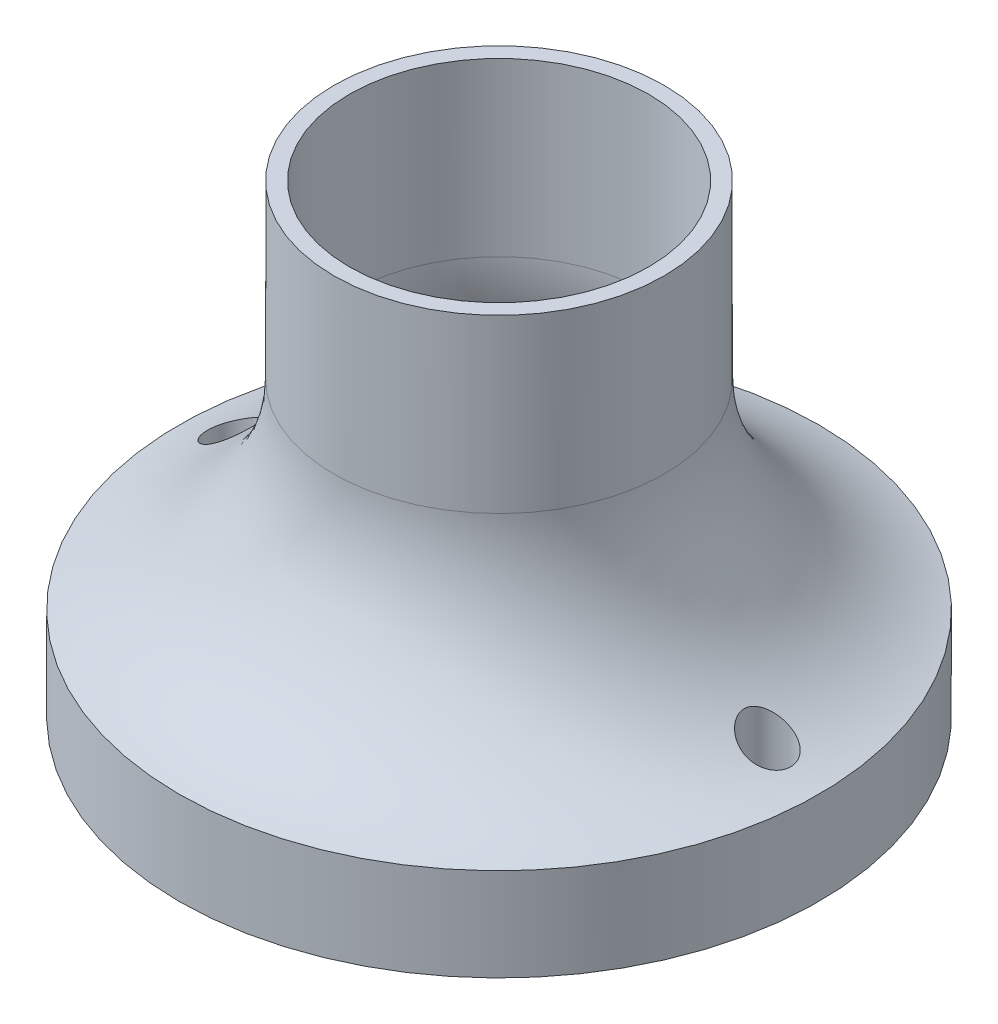
SolidWorks part; units mm, degrees
ref_plane "Front Plane" through (0, 0, 0) normal (0, 0, 1) x (1, 0, 0)
ref_plane "Top Plane" through (0, 0, 0) normal (0, 1, 0) x (1, 0, 0)
ref_plane "Right Plane" through (0, 0, 0) normal (1, 0, 0) x (0, 0, -1)
sketch "Sketch1" plane through (0, 0, 0) normal (0, 1, 0) x (1, 0, 0)
  circle A0 centre (0, 0) radius 31
  dimension "D1" = 62
extrude "Boss-Extrude1" add sketch "Sketch1" along normal blind 9
sketch "Sketch2" plane through (0, 9, 0) normal (0, 1, 0) x (1, 0, 0)
  circle A0 centre (0, 0) radius 16
  dimension "D1" = 32
extrude "Boss-Extrude2" add sketch "Sketch2" along normal blind 36
fillet "Fillet1" radius 20 1 edges at (0, 9, 16)
hole_wizard "Ø4.5 (4.5) Diameter Hole1" positions "Sketch5" profile "Sketch4" hole size "Ø4.5" standard "ISO" end condition through all
sketch "Sketch5" plane through (0, 0, 0) normal (0, -1, 0) x (-1, 0, 0)
  line L0 (26, 0) -> (-26, 0) construction
  point P1 (26, 0)
  point P2 (-26, 0)
  dimension "D1" = 52
sketch "Sketch4" plane through (-26, 0, 0) normal (1, 0, 0) x (0, 0, -1)
  line L0 (0, 0) -> (0, 45)
  line L1 (0, 45) -> (2.25, 45)
  line L2 (2.25, 45) -> (2.25, 0)
  line L5 (2.25, 0) -> (0, 0)
  line L11 (0, -6.35) -> (0, 107.95) construction
  dimension "Thru Hole Dia." = 4.5
  dimension "Thru Hole Depth" = 45
shell "Shell1" thickness 1.5 removed face at (0, 45, 16) removed face at (-26, 0, -2.25)
